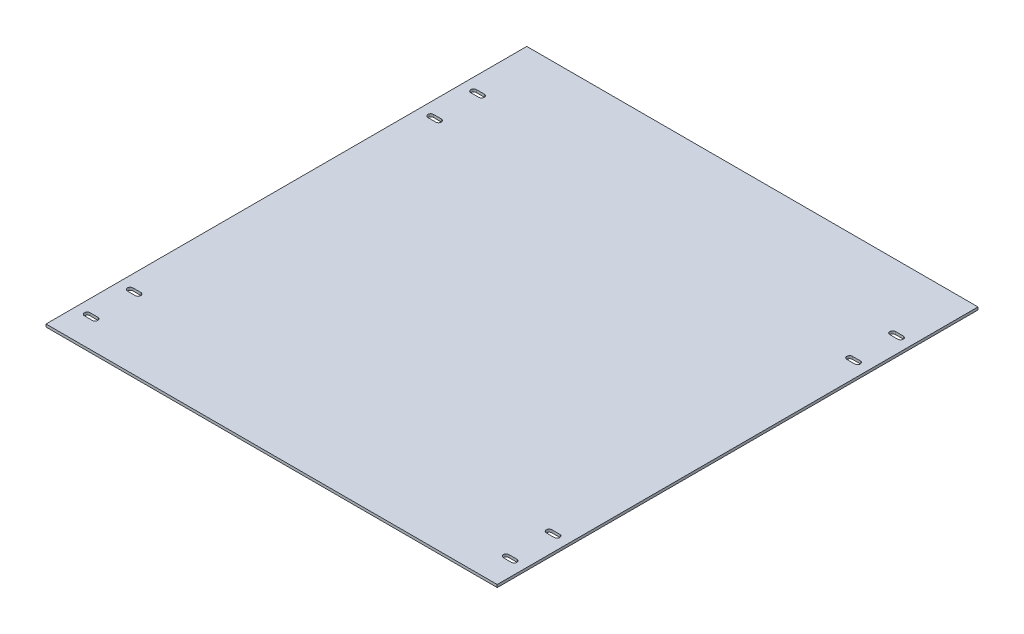
SolidWorks part; units mm, degrees
material "PC High Viscosity"
ref_plane "Front Plane" through (0, 0, 0) normal (0, 0, 1) x (1, 0, 0)
ref_plane "Top Plane" through (0, 0, 0) normal (0, 1, 0) x (1, 0, 0)
ref_plane "Right Plane" through (0, 0, 0) normal (1, 0, 0) x (0, 0, -1)
sketch "Sketch1" plane through (0, 0, 0) normal (0, 1, 0) x (1, 0, 0)
  line L1 (-266.7, -284.1625) -> (266.7, -284.1625)
  line L2 (-266.7, -284.1625) -> (-266.7, 284.1625)
  line L3 (-266.7, 284.1625) -> (266.7, 284.1625)
  line L4 (266.7, -284.1625) -> (266.7, 284.1625)
  line L5 (-266.7, -284.1625) -> (266.7, 284.1625) construction
  line L6 (-266.7, 284.1625) -> (266.7, -284.1625) construction
  point P0 (0, 0)
  dimension "D1" = 533.4
  dimension "D2" = 568.325
extrude "Boss-Extrude1" add sketch "Sketch1" along normal blind 3.175
sketch "Sketch2" plane through (0, 3.175, 0) normal (0, 1, 0) x (1, 0, 0)
  line L0 (-247.65, 284.1625) -> (-247.65, -284.1625) construction
  line L2 (247.65, 284.1625) -> (247.65, -284.1625) construction
  line L3 (266.7, 284.1625) -> (-266.7, 284.1625) construction
  line L4 (0, 284.1625) -> (0, -284.1625) construction
  line L5 (-266.7, -284.1625) -> (266.7, -284.1625) construction
  point P2 (247.65, 156.1465)
  point P4 (-247.65, -249.8725)
  point P13 (-247.65, 206.9465)
  point P16 (-247.65, -199.0725)
  point P17 (-247.65, 156.1465)
  point P22 (247.65, -199.0725)
  point P25 (247.65, 206.9465)
  point P26 (247.65, -249.8725)
  dimension "D2" = 247.65
  dimension "D7" = 34.29
  dimension "D8" = 50.8
  dimension "D9" = 50.8
  dimension "D10" = 77.216
hole_wizard "F (0.257) Diameter Slot1" positions "Sketch3" profile "Sketch4" size "F" standard "ANSI Inch" slot yes end condition through all
sketch "Sketch3" plane through (0, 3.175, 0) normal (0, 1, 0) x (1, 0, 0)
  line L0 (-255.5875, 206.9465) -> (-239.7125, 206.9465) construction
  point P0 (-247.65, 206.9465)
  point P3 (-247.65, 156.1465)
  point P6 (-247.65, -199.0725)
  point P9 (-247.65, -249.8725)
  point P12 (247.65, -249.8725)
  point P15 (247.65, -199.0725)
  point P18 (247.65, 156.1465)
  point P21 (247.65, 206.9465)
  dimension "D1" = 15.875
sketch "Sketch4" plane through (-247.65, 3.175, -206.9465) normal (1, 0, 0) x (0, 0, 1)
  line L0 (0, 0) -> (0, 3.175)
  line L1 (0, 3.175) -> (3.2639, 3.175)
  line L2 (3.2639, 3.175) -> (3.2639, 0)
  line L5 (3.2639, 0) -> (0, 0)
  line L11 (0, -6.35) -> (0, 107.95) construction
  dimension "Thru Hole Dia." = 6.5278
  dimension "Thru Hole Depth" = 3.175
